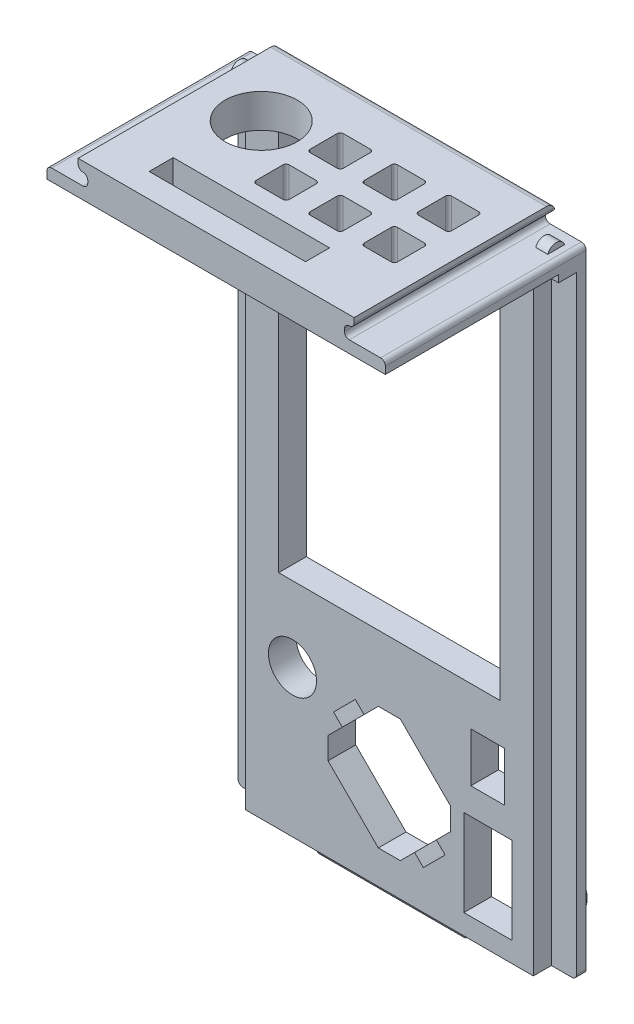
SolidWorks part; units mm, degrees
note: The reader was unsure of these and kept them because the rebuilt part matched: shared geometry of "草图2<3>".
ref_plane "前视基准面" through (0, 0, 0) normal (0, 0, 1) x (1, 0, 0)
ref_plane "上视基准面" through (0, 0, 0) normal (0, 1, 0) x (1, 0, 0)
ref_plane "右视基准面" through (0, 0, 0) normal (1, 0, 0) x (0, 0, -1)
sketch "草图1" plane through (0, 0, 0) normal (0, 0, 1) x (1, 0, 0)
  line L0 (0, -50.8) -> (0, 0)
  line L1 (0, -50.8) -> (27.94, -50.8)
  line L2 (27.94, -50.8) -> (27.94, 0)
  line L3 (0, 0) -> (27.94, 0)
  line L4 (14.67, -38.27) -> (13.27, -38.27)
  line L5 (13.27, -38.27) -> (13.97, -37.37)
  line L6 (13.97, -37.37) -> (14.67, -38.27)
  line L7 (18.77, -43.77) -> (18.77, -42.37)
  line L8 (18.77, -42.37) -> (19.67, -43.07)
  line L9 (19.67, -43.07) -> (18.77, -43.77)
  line L10 (9.17, -42.37) -> (9.17, -43.77)
  line L11 (9.17, -43.77) -> (8.27, -43.07)
  line L12 (8.27, -43.07) -> (9.17, -42.37)
  line L13 (13.27, -47.87) -> (14.67, -47.87)
  line L14 (14.67, -47.87) -> (13.97, -48.77)
  line L15 (13.97, -48.77) -> (13.27, -47.87)
  line L16 (4.5291, -38.6112) -> (4.5835, -38.6112)
  line L17 (4.5835, -38.6112) -> (4.5835, -38.6384)
  line L18 (4.5835, -38.6384) -> (4.6108, -38.6384)
  line L19 (4.6108, -38.6384) -> (4.6108, -38.6657)
  line L20 (4.6108, -38.6657) -> (4.638, -38.6657)
  line L21 (4.638, -38.6657) -> (4.638, -38.7201)
  line L22 (4.638, -38.7201) -> (4.6653, -38.7201)
  line L23 (4.6653, -38.7201) -> (4.6653, -38.9381)
  line L24 (4.6653, -38.9381) -> (4.6925, -38.9381)
  line L25 (4.6925, -38.9381) -> (4.6925, -39.1015)
  line L26 (4.6925, -39.1015) -> (4.7197, -39.1015)
  line L27 (4.7197, -39.1015) -> (4.7197, -39.1832)
  line L28 (4.7197, -39.1832) -> (4.747, -39.1832)
  line L29 (4.747, -39.1832) -> (4.747, -39.2921)
  line L30 (4.747, -39.2921) -> (4.7742, -39.2921)
  line L31 (4.7742, -39.2921) -> (4.7742, -39.3466)
  line L32 (4.7742, -39.3466) -> (4.8014, -39.3466)
  line L33 (4.8014, -39.3466) -> (4.8014, -39.3739)
  line L34 (4.8014, -39.3739) -> (4.8287, -39.3739)
  line L35 (4.8287, -39.3739) -> (4.8287, -39.4283)
  line L36 (4.8287, -39.4283) -> (4.8559, -39.4283)
  line L37 (4.8559, -39.4283) -> (4.8559, -39.4828)
  line L38 (4.8559, -39.4828) -> (4.8832, -39.4828)
  line L39 (4.8832, -39.4828) -> (4.8832, -39.51)
  line L40 (4.8832, -39.51) -> (4.9104, -39.51)
  line L41 (4.9104, -39.51) -> (4.9104, -39.5373)
  line L42 (4.9104, -39.5373) -> (4.9376, -39.5373)
  line L43 (4.9376, -39.5373) -> (4.9376, -39.5918)
  line L44 (4.9376, -39.5918) -> (4.9649, -39.5918)
  line L45 (4.9649, -39.5918) -> (4.9649, -39.619)
  line L46 (4.9649, -39.619) -> (4.9921, -39.619)
  line L47 (4.9921, -39.619) -> (4.9921, -39.6462)
  line L48 (4.9921, -39.6462) -> (5.0193, -39.6462)
  line L49 (5.0193, -39.6462) -> (5.0193, -39.6735)
  line L50 (5.0193, -39.6735) -> (5.0466, -39.6735)
  line L51 (5.0466, -39.6735) -> (5.0466, -39.7007)
  line L52 (5.0466, -39.7007) -> (5.0738, -39.7007)
  line L53 (5.0738, -39.7007) -> (5.0738, -39.7279)
  line L54 (5.0738, -39.7279) -> (5.1011, -39.7279)
  line L55 (5.1011, -39.7279) -> (5.1011, -39.7552)
  line L56 (5.1011, -39.7552) -> (5.1283, -39.7552)
  line L57 (5.1283, -39.7552) -> (5.1283, -39.7824)
  line L58 (5.1283, -39.7824) -> (5.1828, -39.7824)
  line L59 (5.1828, -39.7824) -> (5.1828, -39.8097)
  line L60 (5.1828, -39.8097) -> (5.21, -39.8097)
  line L61 (5.21, -39.8097) -> (5.21, -39.8369)
  line L62 (5.21, -39.8369) -> (5.2645, -39.8369)
  line L63 (5.2645, -39.8369) -> (5.2645, -39.8641)
  line L64 (5.2645, -39.8641) -> (5.319, -39.8641)
  line L65 (5.319, -39.8641) -> (5.319, -39.8914)
  line L66 (5.319, -39.8914) -> (5.3462, -39.8914)
  line L67 (5.3462, -39.8914) -> (5.3462, -39.9186)
  line L68 (5.3462, -39.9186) -> (5.4007, -39.9186)
  line L69 (5.4007, -39.9186) -> (5.4007, -39.9459)
  line L70 (5.4007, -39.9459) -> (5.4824, -39.9459)
  line L71 (5.4824, -39.9459) -> (5.4824, -39.9731)
  line L72 (5.4824, -39.9731) -> (5.5913, -39.9731)
  line L73 (5.5913, -39.9731) -> (5.5913, -40.0003)
  line L74 (5.5913, -40.0003) -> (5.7003, -40.0003)
  line L75 (5.7003, -40.0003) -> (5.7003, -40.0276)
  line L76 (5.7003, -40.0276) -> (6.1361, -40.0276)
  line L77 (6.1361, -40.0276) -> (6.1361, -40.0003)
  line L78 (6.1361, -40.0003) -> (6.2451, -40.0003)
  line L79 (6.2451, -40.0003) -> (6.2451, -39.9731)
  line L80 (6.2451, -39.9731) -> (6.354, -39.9731)
  line L81 (6.354, -39.9731) -> (6.354, -39.9459)
  line L82 (6.354, -39.9459) -> (6.4085, -39.9459)
  line L83 (6.4085, -39.9459) -> (6.4085, -39.9186)
  line L84 (6.4085, -39.9186) -> (6.463, -39.9186)
  line L85 (6.463, -39.9186) -> (6.463, -39.8914)
  line L86 (6.463, -39.8914) -> (6.5174, -39.8914)
  line L87 (6.5174, -39.8914) -> (6.5174, -39.8641)
  line L88 (6.5174, -39.8641) -> (6.5719, -39.8641)
  line L89 (6.5719, -39.8641) -> (6.5719, -39.8369)
  line L90 (6.5719, -39.8369) -> (6.6264, -39.8369)
  line L91 (6.6264, -39.8369) -> (6.6264, -39.8097)
  line L92 (6.6264, -39.8097) -> (6.6536, -39.8097)
  line L93 (6.6536, -39.8097) -> (6.6536, -39.7824)
  line L94 (6.6536, -39.7824) -> (6.6809, -39.7824)
  line L95 (6.6809, -39.7824) -> (6.6809, -39.7552)
  line L96 (6.6809, -39.7552) -> (6.7353, -39.7552)
  line L97 (6.7353, -39.7552) -> (6.7353, -39.7279)
  line L98 (6.7353, -39.7279) -> (6.7626, -39.7279)
  line L99 (6.7626, -39.7279) -> (6.7626, -39.7007)
  line L100 (6.7626, -39.7007) -> (6.7898, -39.7007)
  line L101 (6.7898, -39.7007) -> (6.7898, -39.6735)
  line L102 (6.7898, -39.6735) -> (6.8171, -39.6735)
  line L103 (6.8171, -39.6735) -> (6.8171, -39.6462)
  line L104 (6.8171, -39.6462) -> (6.8443, -39.6462)
  line L105 (6.8443, -39.6462) -> (6.8443, -39.619)
  line L106 (6.8443, -39.619) -> (6.8715, -39.619)
  line L107 (6.8715, -39.619) -> (6.8715, -39.5645)
  line L108 (6.8715, -39.5645) -> (6.8988, -39.5645)
  line L109 (6.8988, -39.5645) -> (6.8988, -39.5373)
  line L110 (6.8988, -39.5373) -> (6.926, -39.5373)
  line L111 (6.926, -39.5373) -> (6.926, -39.51)
  line L112 (6.926, -39.51) -> (6.9532, -39.51)
  line L113 (6.9532, -39.51) -> (6.9532, -39.4828)
  line L114 (6.9532, -39.4828) -> (6.9805, -39.4828)
  line L115 (6.9805, -39.4828) -> (6.9805, -39.4283)
  line L116 (6.9805, -39.4283) -> (7.0077, -39.4283)
  line L117 (7.0077, -39.4283) -> (7.0077, -39.3739)
  line L118 (7.0077, -39.3739) -> (7.035, -39.3739)
  line L119 (7.035, -39.3739) -> (7.035, -39.3194)
  line L120 (7.035, -39.3194) -> (7.0622, -39.3194)
  line L121 (7.0622, -39.3194) -> (7.0622, -39.2649)
  line L122 (7.0622, -39.2649) -> (7.0894, -39.2649)
  line L123 (7.0894, -39.2649) -> (7.0894, -39.1832)
  line L124 (7.0894, -39.1832) -> (7.1167, -39.1832)
  line L125 (7.1167, -39.1832) -> (7.1167, -39.1015)
  line L126 (7.1167, -39.1015) -> (7.1439, -39.1015)
  line L127 (7.1439, -39.1015) -> (7.1439, -38.9381)
  line L128 (7.1439, -38.9381) -> (7.1711, -38.9381)
  line L129 (7.1711, -38.9381) -> (7.1711, -38.7746)
  line L130 (7.1711, -38.7746) -> (7.1984, -38.7746)
  line L131 (7.1984, -38.7746) -> (7.1984, -38.7201)
  line L132 (7.1984, -38.7201) -> (7.2256, -38.7201)
  line L133 (7.2256, -38.7201) -> (7.2256, -38.6929)
  line L134 (7.2256, -38.6929) -> (7.2529, -38.6929)
  line L135 (7.2529, -38.6929) -> (7.2529, -38.6657)
  line L136 (7.2529, -38.6657) -> (7.4163, -38.6657)
  line L137 (7.4163, -38.6657) -> (7.4163, -38.6929)
  line L138 (7.4163, -38.6929) -> (7.4708, -38.6929)
  line L139 (7.4708, -38.6929) -> (7.4708, -38.7474)
  line L140 (7.4708, -38.7474) -> (7.498, -38.7474)
  line L141 (7.498, -38.7474) -> (7.498, -38.8019)
  line L142 (7.498, -38.8019) -> (7.5252, -38.8019)
  line L143 (7.5252, -38.8019) -> (7.5252, -38.8563)
  line L144 (7.5252, -38.8563) -> (7.498, -38.8563)
  line L145 (7.498, -38.8563) -> (7.498, -39.0742)
  line L146 (7.498, -39.0742) -> (7.4708, -39.0742)
  line L147 (7.4708, -39.0742) -> (7.4708, -39.1832)
  line L148 (7.4708, -39.1832) -> (7.4435, -39.1832)
  line L149 (7.4435, -39.1832) -> (7.4435, -39.2649)
  line L150 (7.4435, -39.2649) -> (7.4163, -39.2649)
  line L151 (7.4163, -39.2649) -> (7.4163, -39.3466)
  line L152 (7.4163, -39.3466) -> (7.389, -39.3466)
  line L153 (7.389, -39.3466) -> (7.389, -39.4283)
  line L154 (7.389, -39.4283) -> (7.3618, -39.4283)
  line L155 (7.3618, -39.4283) -> (7.3618, -39.4828)
  line L156 (7.3618, -39.4828) -> (7.3346, -39.4828)
  line L157 (7.3346, -39.4828) -> (7.3346, -39.5373)
  line L158 (7.3346, -39.5373) -> (7.3073, -39.5373)
  line L159 (7.3073, -39.5373) -> (7.3073, -39.5918)
  line L160 (7.3073, -39.5918) -> (7.2801, -39.5918)
  line L161 (7.2801, -39.5918) -> (7.2801, -39.6462)
  line L162 (7.2801, -39.6462) -> (7.2529, -39.6462)
  line L163 (7.2529, -39.6462) -> (7.2529, -39.6735)
  line L164 (7.2529, -39.6735) -> (7.2256, -39.6735)
  line L165 (7.2256, -39.6735) -> (7.2256, -39.7007)
  line L166 (7.2256, -39.7007) -> (7.1984, -39.7007)
  line L167 (7.1984, -39.7007) -> (7.1984, -39.7552)
  line L168 (7.1984, -39.7552) -> (7.1711, -39.7552)
  line L169 (7.1711, -39.7552) -> (7.1711, -39.7824)
  line L170 (7.1711, -39.7824) -> (7.1439, -39.7824)
  line L171 (7.1439, -39.7824) -> (7.1439, -39.8097)
  line L172 (7.1439, -39.8097) -> (7.1167, -39.8097)
  line L173 (7.1167, -39.8097) -> (7.1167, -39.8641)
  line L174 (7.1167, -39.8641) -> (7.0894, -39.8641)
  line L175 (7.0894, -39.8641) -> (7.0894, -39.8914)
  line L176 (7.0894, -39.8914) -> (7.035, -39.8914)
  line L177 (7.035, -39.8914) -> (7.035, -39.9186)
  line L178 (7.035, -39.9186) -> (7.0077, -39.9186)
  line L179 (7.0077, -39.9186) -> (7.0077, -39.9459)
  line L180 (7.0077, -39.9459) -> (6.9805, -39.9459)
  line L181 (6.9805, -39.9459) -> (6.9805, -39.9731)
  line L182 (6.9805, -39.9731) -> (6.9532, -39.9731)
  line L183 (6.9532, -39.9731) -> (6.9532, -40.0003)
  line L184 (6.9532, -40.0003) -> (6.926, -40.0003)
  line L185 (6.926, -40.0003) -> (6.926, -40.0276)
  line L186 (6.926, -40.0276) -> (6.8988, -40.0276)
  line L187 (6.8988, -40.0276) -> (6.8988, -40.0548)
  line L188 (6.8988, -40.0548) -> (6.8443, -40.0548)
  line L189 (6.8443, -40.0548) -> (6.8443, -40.082)
  line L190 (6.8443, -40.082) -> (6.8171, -40.082)
  line L191 (6.8171, -40.082) -> (6.8171, -40.1093)
  line L192 (6.8171, -40.1093) -> (6.7626, -40.1093)
  line L193 (6.7626, -40.1093) -> (6.7626, -40.1365)
  line L194 (6.7626, -40.1365) -> (6.7353, -40.1365)
  line L195 (6.7353, -40.1365) -> (6.7353, -40.1638)
  line L196 (6.7353, -40.1638) -> (6.6809, -40.1638)
  line L197 (6.6809, -40.1638) -> (6.6809, -40.191)
  line L198 (6.6809, -40.191) -> (6.6264, -40.191)
  line L199 (6.6264, -40.191) -> (6.6264, -40.2182)
  line L200 (6.6264, -40.2182) -> (6.5719, -40.2182)
  line L201 (6.5719, -40.2182) -> (6.5719, -40.2455)
  line L202 (6.5719, -40.2455) -> (6.5174, -40.2455)
  line L203 (6.5174, -40.2455) -> (6.5174, -40.2727)
  line L204 (6.5174, -40.2727) -> (6.4357, -40.2727)
  line L205 (6.4357, -40.2727) -> (6.4357, -40.2999)
  line L206 (6.4357, -40.2999) -> (6.354, -40.2999)
  line L207 (6.354, -40.2999) -> (6.354, -40.3272)
  line L208 (6.354, -40.3272) -> (6.2178, -40.3272)
  line L209 (6.2178, -40.3272) -> (6.2178, -40.3544)
  line L210 (6.2178, -40.3544) -> (6.1089, -40.3544)
  line L211 (6.1089, -40.3544) -> (6.1089, -40.7902)
  line L212 (6.1089, -40.7902) -> (6.4357, -40.7902)
  line L213 (6.4357, -40.7902) -> (6.4357, -40.8175)
  line L214 (6.4357, -40.8175) -> (6.5174, -40.8175)
  line L215 (6.5174, -40.8175) -> (6.5174, -40.8447)
  line L216 (6.5174, -40.8447) -> (6.5447, -40.8447)
  line L217 (6.5447, -40.8447) -> (6.5447, -40.8719)
  line L218 (6.5447, -40.8719) -> (6.5719, -40.8719)
  line L219 (6.5719, -40.8719) -> (6.5719, -40.8992)
  line L220 (6.5719, -40.8992) -> (6.5991, -40.8992)
  line L221 (6.5991, -40.8992) -> (6.5991, -41.0898)
  line L222 (6.5991, -41.0898) -> (6.5719, -41.0898)
  line L223 (6.5719, -41.0898) -> (6.5719, -41.1443)
  line L224 (6.5719, -41.1443) -> (6.5447, -41.1443)
  line L225 (6.5447, -41.1443) -> (6.5447, -41.1716)
  line L226 (6.5447, -41.1716) -> (6.4902, -41.1716)
  line L227 (6.4902, -41.1716) -> (6.4902, -41.1988)
  line L228 (6.4902, -41.1988) -> (5.3462, -41.1988)
  line L229 (5.3462, -41.1988) -> (5.3462, -41.1716)
  line L230 (5.3462, -41.1716) -> (5.2917, -41.1716)
  line L231 (5.2917, -41.1716) -> (5.2917, -41.1443)
  line L232 (5.2917, -41.1443) -> (5.2645, -41.1443)
  line L233 (5.2645, -41.1443) -> (5.2645, -41.0898)
  line L234 (5.2645, -41.0898) -> (5.2372, -41.0898)
  line L235 (5.2372, -41.0898) -> (5.2372, -40.8992)
  line L236 (5.2372, -40.8992) -> (5.2645, -40.8992)
  line L237 (5.2645, -40.8992) -> (5.2645, -40.8719)
  line L238 (5.2645, -40.8719) -> (5.2917, -40.8719)
  line L239 (5.2917, -40.8719) -> (5.2917, -40.8447)
  line L240 (5.2917, -40.8447) -> (5.319, -40.8447)
  line L241 (5.319, -40.8447) -> (5.319, -40.8175)
  line L242 (5.319, -40.8175) -> (5.4007, -40.8175)
  line L243 (5.4007, -40.8175) -> (5.4007, -40.7902)
  line L244 (5.4007, -40.7902) -> (5.7003, -40.7902)
  line L245 (5.7003, -40.7902) -> (5.7003, -40.3544)
  line L246 (5.7003, -40.3544) -> (5.5913, -40.3544)
  line L247 (5.5913, -40.3544) -> (5.5913, -40.3272)
  line L248 (5.5913, -40.3272) -> (5.4824, -40.3272)
  line L249 (5.4824, -40.3272) -> (5.4824, -40.2999)
  line L250 (5.4824, -40.2999) -> (5.4007, -40.2999)
  line L251 (5.4007, -40.2999) -> (5.4007, -40.2727)
  line L252 (5.4007, -40.2727) -> (5.319, -40.2727)
  line L253 (5.319, -40.2727) -> (5.319, -40.2455)
  line L254 (5.319, -40.2455) -> (5.2645, -40.2455)
  line L255 (5.2645, -40.2455) -> (5.2645, -40.2182)
  line L256 (5.2645, -40.2182) -> (5.21, -40.2182)
  line L257 (5.21, -40.2182) -> (5.21, -40.191)
  line L258 (5.21, -40.191) -> (5.1555, -40.191)
  line L259 (5.1555, -40.191) -> (5.1555, -40.1638)
  line L260 (5.1555, -40.1638) -> (5.1011, -40.1638)
  line L261 (5.1011, -40.1638) -> (5.1011, -40.1365)
  line L262 (5.1011, -40.1365) -> (5.0466, -40.1365)
  line L263 (5.0466, -40.1365) -> (5.0466, -40.1093)
  line L264 (5.0466, -40.1093) -> (5.0193, -40.1093)
  line L265 (5.0193, -40.1093) -> (5.0193, -40.082)
  line L266 (5.0193, -40.082) -> (4.9649, -40.082)
  line L267 (4.9649, -40.082) -> (4.9649, -40.0548)
  line L268 (4.9649, -40.0548) -> (4.9376, -40.0548)
  line L269 (4.9376, -40.0548) -> (4.9376, -40.0276)
  line L270 (4.9376, -40.0276) -> (4.9104, -40.0276)
  line L271 (4.9104, -40.0276) -> (4.9104, -40.0003)
  line L272 (4.9104, -40.0003) -> (4.8832, -40.0003)
  line L273 (4.8832, -40.0003) -> (4.8832, -39.9731)
  line L274 (4.8832, -39.9731) -> (4.8287, -39.9731)
  line L275 (4.8287, -39.9731) -> (4.8287, -39.9459)
  line L276 (4.8287, -39.9459) -> (4.8014, -39.9459)
  line L277 (4.8014, -39.9459) -> (4.8014, -39.9186)
  line L278 (4.8014, -39.9186) -> (4.7742, -39.9186)
  line L279 (4.7742, -39.9186) -> (4.7742, -39.8914)
  line L280 (4.7742, -39.8914) -> (4.747, -39.8914)
  line L281 (4.747, -39.8914) -> (4.747, -39.8641)
  line L282 (4.747, -39.8641) -> (4.7197, -39.8641)
  line L283 (4.7197, -39.8641) -> (4.7197, -39.8097)
  line L284 (4.7197, -39.8097) -> (4.6925, -39.8097)
  line L285 (4.6925, -39.8097) -> (4.6925, -39.7824)
  line L286 (4.6925, -39.7824) -> (4.6653, -39.7824)
  line L287 (4.6653, -39.7824) -> (4.6653, -39.7552)
  line L288 (4.6653, -39.7552) -> (4.638, -39.7552)
  line L289 (4.638, -39.7552) -> (4.638, -39.7279)
  line L290 (4.638, -39.7279) -> (4.6108, -39.7279)
  line L291 (4.6108, -39.7279) -> (4.6108, -39.6735)
  line L292 (4.6108, -39.6735) -> (4.5835, -39.6735)
  line L293 (4.5835, -39.6735) -> (4.5835, -39.6462)
  line L294 (4.5835, -39.6462) -> (4.5563, -39.6462)
  line L295 (4.5563, -39.6462) -> (4.5563, -39.5918)
  line L296 (4.5563, -39.5918) -> (4.5291, -39.5918)
  line L297 (4.5291, -39.5918) -> (4.5291, -39.5645)
  line L298 (4.5291, -39.5645) -> (4.5018, -39.5645)
  line L299 (4.5018, -39.5645) -> (4.5018, -39.51)
  line L300 (4.5018, -39.51) -> (4.4746, -39.51)
  line L301 (4.4746, -39.51) -> (4.4746, -39.4283)
  line L302 (4.4746, -39.4283) -> (4.4473, -39.4283)
  line L303 (4.4473, -39.4283) -> (4.4473, -39.3739)
  line L304 (4.4473, -39.3739) -> (4.4201, -39.3739)
  line L305 (4.4201, -39.3739) -> (4.4201, -39.2921)
  line L306 (4.4201, -39.2921) -> (4.3929, -39.2921)
  line L307 (4.3929, -39.2921) -> (4.3929, -39.2104)
  line L308 (4.3929, -39.2104) -> (4.3656, -39.2104)
  line L309 (4.3656, -39.2104) -> (4.3656, -39.1015)
  line L310 (4.3656, -39.1015) -> (4.3384, -39.1015)
  line L311 (4.3384, -39.1015) -> (4.3384, -38.8836)
  line L312 (4.3384, -38.8836) -> (4.3112, -38.8836)
  line L313 (4.3112, -38.8836) -> (4.3112, -38.7474)
  line L314 (4.3112, -38.7474) -> (4.3384, -38.7474)
  line L315 (4.3384, -38.7474) -> (4.3384, -38.6657)
  line L316 (4.3384, -38.6657) -> (4.3656, -38.6657)
  line L317 (4.3656, -38.6657) -> (4.3656, -38.6384)
  line L318 (4.3656, -38.6384) -> (4.3929, -38.6384)
  line L319 (4.3929, -38.6384) -> (4.3929, -38.6112)
  line L320 (4.3929, -38.6112) -> (4.4473, -38.6112)
  line L321 (4.4473, -38.6112) -> (4.4473, -38.584)
  line L322 (4.4473, -38.584) -> (4.5291, -38.584)
  line L323 (4.5291, -38.584) -> (4.5291, -38.6112)
  line L324 (6.0544, -36.5411) -> (6.1633, -36.5411)
  line L325 (6.1633, -36.5411) -> (6.1633, -36.5683)
  line L326 (6.1633, -36.5683) -> (6.2451, -36.5683)
  line L327 (6.2451, -36.5683) -> (6.2451, -36.5956)
  line L328 (6.2451, -36.5956) -> (6.2995, -36.5956)
  line L329 (6.2995, -36.5956) -> (6.2995, -36.6228)
  line L330 (6.2995, -36.6228) -> (6.354, -36.6228)
  line L331 (6.354, -36.6228) -> (6.354, -36.6501)
  line L332 (6.354, -36.6501) -> (6.3812, -36.6501)
  line L333 (6.3812, -36.6501) -> (6.3812, -36.6773)
  line L334 (6.3812, -36.6773) -> (6.4357, -36.6773)
  line L335 (6.4357, -36.6773) -> (6.4357, -36.7045)
  line L336 (6.4357, -36.7045) -> (6.463, -36.7045)
  line L337 (6.463, -36.7045) -> (6.463, -36.7318)
  line L338 (6.463, -36.7318) -> (6.4902, -36.7318)
  line L339 (6.4902, -36.7318) -> (6.4902, -36.759)
  line L340 (6.4902, -36.759) -> (6.5174, -36.759)
  line L341 (6.5174, -36.759) -> (6.5174, -36.7863)
  line L342 (6.5174, -36.7863) -> (6.5447, -36.7863)
  line L343 (6.5447, -36.7863) -> (6.5447, -36.8135)
  line L344 (6.5447, -36.8135) -> (6.5719, -36.8135)
  line L345 (6.5719, -36.8135) -> (6.5719, -36.868)
  line L346 (6.5719, -36.868) -> (6.5991, -36.868)
  line L347 (6.5991, -36.868) -> (6.5991, -36.8952)
  line L348 (6.5991, -36.8952) -> (6.6264, -36.8952)
  line L349 (6.6264, -36.8952) -> (6.6264, -36.9497)
  line L350 (6.6264, -36.9497) -> (6.6536, -36.9497)
  line L351 (6.6536, -36.9497) -> (6.6536, -36.9769)
  line L352 (6.6536, -36.9769) -> (6.6809, -36.9769)
  line L353 (6.6809, -36.9769) -> (6.6809, -37.0314)
  line L354 (6.6809, -37.0314) -> (6.7081, -37.0314)
  line L355 (6.7081, -37.0314) -> (6.7081, -37.1403)
  line L356 (6.7081, -37.1403) -> (6.7353, -37.1403)
  line L357 (6.7353, -37.1403) -> (6.7353, -38.9925)
  line L358 (6.7353, -38.9925) -> (6.7081, -38.9925)
  line L359 (6.7081, -38.9925) -> (6.7081, -39.0742)
  line L360 (6.7081, -39.0742) -> (6.6809, -39.0742)
  line L361 (6.6809, -39.0742) -> (6.6809, -39.156)
  line L362 (6.6809, -39.156) -> (6.6536, -39.156)
  line L363 (6.6536, -39.156) -> (6.6536, -39.1832)
  line L364 (6.6536, -39.1832) -> (6.6264, -39.1832)
  line L365 (6.6264, -39.1832) -> (6.6264, -39.2377)
  line L366 (6.6264, -39.2377) -> (6.5991, -39.2377)
  line L367 (6.5991, -39.2377) -> (6.5991, -39.2921)
  line L368 (6.5991, -39.2921) -> (6.5719, -39.2921)
  line L369 (6.5719, -39.2921) -> (6.5719, -39.3194)
  line L370 (6.5719, -39.3194) -> (6.5447, -39.3194)
  line L371 (6.5447, -39.3194) -> (6.5447, -39.3466)
  line L372 (6.5447, -39.3466) -> (6.5174, -39.3466)
  line L373 (6.5174, -39.3466) -> (6.5174, -39.3739)
  line L374 (6.5174, -39.3739) -> (6.4902, -39.3739)
  line L375 (6.4902, -39.3739) -> (6.4902, -39.4011)
  line L376 (6.4902, -39.4011) -> (6.463, -39.4011)
  line L377 (6.463, -39.4011) -> (6.463, -39.4283)
  line L378 (6.463, -39.4283) -> (6.4357, -39.4283)
  line L379 (6.4357, -39.4283) -> (6.4357, -39.4556)
  line L380 (6.4357, -39.4556) -> (6.3812, -39.4556)
  line L381 (6.3812, -39.4556) -> (6.3812, -39.4828)
  line L382 (6.3812, -39.4828) -> (6.354, -39.4828)
  line L383 (6.354, -39.4828) -> (6.354, -39.51)
  line L384 (6.354, -39.51) -> (6.2995, -39.51)
  line L385 (6.2995, -39.51) -> (6.2995, -39.5373)
  line L386 (6.2995, -39.5373) -> (6.2451, -39.5373)
  line L387 (6.2451, -39.5373) -> (6.2451, -39.5645)
  line L388 (6.2451, -39.5645) -> (6.1633, -39.5645)
  line L389 (6.1633, -39.5645) -> (6.1633, -39.5918)
  line L390 (6.1633, -39.5918) -> (6.0544, -39.5918)
  line L391 (6.0544, -39.5918) -> (6.0544, -39.619)
  line L392 (6.0544, -39.619) -> (5.782, -39.619)
  line L393 (5.782, -39.619) -> (5.782, -39.5918)
  line L394 (5.782, -39.5918) -> (5.6731, -39.5918)
  line L395 (5.6731, -39.5918) -> (5.6731, -39.5645)
  line L396 (5.6731, -39.5645) -> (5.5913, -39.5645)
  line L397 (5.5913, -39.5645) -> (5.5913, -39.5373)
  line L398 (5.5913, -39.5373) -> (5.5369, -39.5373)
  line L399 (5.5369, -39.5373) -> (5.5369, -39.51)
  line L400 (5.5369, -39.51) -> (5.4824, -39.51)
  line L401 (5.4824, -39.51) -> (5.4824, -39.4828)
  line L402 (5.4824, -39.4828) -> (5.4279, -39.4828)
  line L403 (5.4279, -39.4828) -> (5.4279, -39.4556)
  line L404 (5.4279, -39.4556) -> (5.4007, -39.4556)
  line L405 (5.4007, -39.4556) -> (5.4007, -39.4283)
  line L406 (5.4007, -39.4283) -> (5.3734, -39.4283)
  line L407 (5.3734, -39.4283) -> (5.3734, -39.4011)
  line L408 (5.3734, -39.4011) -> (5.3462, -39.4011)
  line L409 (5.3462, -39.4011) -> (5.3462, -39.3739)
  line L410 (5.3462, -39.3739) -> (5.319, -39.3739)
  line L411 (5.319, -39.3739) -> (5.319, -39.3466)
  line L412 (5.319, -39.3466) -> (5.2917, -39.3466)
  line L413 (5.2917, -39.3466) -> (5.2917, -39.3194)
  line L414 (5.2917, -39.3194) -> (5.2645, -39.3194)
  line L415 (5.2645, -39.3194) -> (5.2645, -39.2921)
  line L416 (5.2645, -39.2921) -> (5.2372, -39.2921)
  line L417 (5.2372, -39.2921) -> (5.2372, -39.2377)
  line L418 (5.2372, -39.2377) -> (5.21, -39.2377)
  line L419 (5.21, -39.2377) -> (5.21, -39.2104)
  line L420 (5.21, -39.2104) -> (5.1828, -39.2104)
  line L421 (5.1828, -39.2104) -> (5.1828, -39.156)
  line L422 (5.1828, -39.156) -> (5.1555, -39.156)
  line L423 (5.1555, -39.156) -> (5.1555, -39.0742)
  line L424 (5.1555, -39.0742) -> (5.1283, -39.0742)
  line L425 (5.1283, -39.0742) -> (5.1283, -38.9925)
  line L426 (5.1283, -38.9925) -> (5.1011, -38.9925)
  line L427 (5.1011, -38.9925) -> (5.1011, -38.8291)
  line L428 (5.1011, -38.8291) -> (5.0738, -38.8291)
  line L429 (5.0738, -38.8291) -> (5.0738, -37.3038)
  line L430 (5.0738, -37.3038) -> (5.1011, -37.3038)
  line L431 (5.1011, -37.3038) -> (5.1011, -37.1403)
  line L432 (5.1011, -37.1403) -> (5.1283, -37.1403)
  line L433 (5.1283, -37.1403) -> (5.1283, -37.0314)
  line L434 (5.1283, -37.0314) -> (5.1555, -37.0314)
  line L435 (5.1555, -37.0314) -> (5.1555, -36.9769)
  line L436 (5.1555, -36.9769) -> (5.1828, -36.9769)
  line L437 (5.1828, -36.9769) -> (5.1828, -36.9224)
  line L438 (5.1828, -36.9224) -> (5.21, -36.9224)
  line L439 (5.21, -36.9224) -> (5.21, -36.868)
  line L440 (5.21, -36.868) -> (5.2372, -36.868)
  line L441 (5.2372, -36.868) -> (5.2372, -36.8407)
  line L442 (5.2372, -36.8407) -> (5.2645, -36.8407)
  line L443 (5.2645, -36.8407) -> (5.2645, -36.8135)
  line L444 (5.2645, -36.8135) -> (5.2917, -36.8135)
  line L445 (5.2917, -36.8135) -> (5.2917, -36.7863)
  line L446 (5.2917, -36.7863) -> (5.319, -36.7863)
  line L447 (5.319, -36.7863) -> (5.319, -36.759)
  line L448 (5.319, -36.759) -> (5.3462, -36.759)
  line L449 (5.3462, -36.759) -> (5.3462, -36.7318)
  line L450 (5.3462, -36.7318) -> (5.3734, -36.7318)
  line L451 (5.3734, -36.7318) -> (5.3734, -36.7045)
  line L452 (5.3734, -36.7045) -> (5.4007, -36.7045)
  line L453 (5.4007, -36.7045) -> (5.4007, -36.6773)
  line L454 (5.4007, -36.6773) -> (5.4279, -36.6773)
  line L455 (5.4279, -36.6773) -> (5.4279, -36.6501)
  line L456 (5.4279, -36.6501) -> (5.4824, -36.6501)
  line L457 (5.4824, -36.6501) -> (5.4824, -36.6228)
  line L458 (5.4824, -36.6228) -> (5.5369, -36.6228)
  line L459 (5.5369, -36.6228) -> (5.5369, -36.5956)
  line L460 (5.5369, -36.5956) -> (5.5913, -36.5956)
  line L461 (5.5913, -36.5956) -> (5.5913, -36.5683)
  line L462 (5.5913, -36.5683) -> (5.6731, -36.5683)
  line L463 (5.6731, -36.5683) -> (5.6731, -36.5411)
  line L464 (5.6731, -36.5411) -> (5.782, -36.5411)
  line L465 (5.782, -36.5411) -> (5.782, -36.5139)
  line L466 (5.782, -36.5139) -> (6.0544, -36.5139)
  line L467 (6.0544, -36.5139) -> (6.0544, -36.5411)
  line L468 (9.4168, 0.0508) -> (9.4168, 2.0508)
  line L469 (5.4168, 2.0508) -> (9.4168, 2.0508)
  line L470 (5.4168, 0.0508) -> (5.4168, 2.0508)
  line L471 (10.4168, -11.9492) -> (10.4168, 0.0508)
  line L472 (4.4148, 0.0508) -> (10.4168, 0.0508)
  line L473 (4.4148, -11.9492) -> (4.4148, 0.0508)
  line L474 (4.4148, -11.9492) -> (10.4168, -11.9492)
  line L475 (20.67, -47.67) -> (20.67, -43.67)
  line L476 (23.67, -47.67) -> (23.67, -43.67)
  line L477 (23.2716, -46.9684) -> (23.2716, -48.7716)
  line L478 (23.2716, -48.7716) -> (21.0684, -48.7716)
  line L479 (21.0684, -48.7716) -> (21.0684, -46.9684)
  line L480 (21.0684, -46.9684) -> (23.2716, -46.9684)
  line L481 (23.2716, -42.5684) -> (23.2716, -44.3716)
  line L482 (23.2716, -44.3716) -> (21.0684, -44.3716)
  line L483 (21.0684, -44.3716) -> (21.0684, -42.5684)
  line L484 (21.0684, -42.5684) -> (23.2716, -42.5684)
  line L485 (16.2151, -45.3235) -> (16.2151, -44.4254)
  line L486 (15.317, -45.3235) -> (16.2151, -44.4254)
  line L487 (15.317, -45.3235) -> (16.2151, -45.3235)
  line L488 (13.97, -43.0784) -> (13.97, -41.6642)
  line L489 (13.97, -41.6642) -> (14.3236, -42.0177)
  line L490 (13.6164, -42.0177) -> (14.3236, -42.0177)
  line L491 (13.6164, -42.0177) -> (13.97, -41.6642)
  line L492 (12.5558, -43.0784) -> (13.97, -43.0784)
  line L493 (12.5558, -43.0784) -> (12.9093, -42.7248)
  line L494 (12.9093, -43.432) -> (12.9093, -42.7248)
  line L495 (12.5558, -43.0784) -> (12.9093, -43.432)
  line L496 (13.97, -44.4926) -> (13.97, -43.0784)
  line L497 (13.6164, -44.1391) -> (13.97, -44.4926)
  line L498 (13.6164, -44.1391) -> (14.3236, -44.1391)
  line L499 (13.97, -44.4926) -> (14.3236, -44.1391)
  line L500 (15.0307, -42.7248) -> (15.3842, -43.0784)
  line L501 (15.0307, -43.432) -> (15.0307, -42.7248)
  line L502 (15.0307, -43.432) -> (15.3842, -43.0784)
  line L503 (13.97, -43.0784) -> (15.3842, -43.0784)
  line L504 (14.6771, -38.4822) -> (18.5662, -42.3713)
  line L505 (13.2629, -38.4822) -> (14.6771, -38.4822)
  line L506 (9.3738, -42.3713) -> (13.2629, -38.4822)
  line L507 (9.3738, -43.7855) -> (13.2629, -47.6746)
  line L508 (9.3738, -43.7855) -> (9.3738, -42.3713)
  line L509 (18.5662, -43.7855) -> (18.5662, -42.3713)
  line L510 (14.6771, -47.6746) -> (18.5662, -43.7855)
  line L511 (13.2629, -47.6746) -> (14.6771, -47.6746)
  line L512 (10.0385, -40.25) -> (11.1416, -39.1469)
  line L513 (11.1416, -39.1469) -> (12.2447, -40.25)
  line L514 (12.2447, -40.25) -> (11.1416, -41.3531)
  line L515 (11.1416, -41.3531) -> (10.0385, -40.25)
  line L516 (15.6953, -45.9068) -> (16.7984, -44.8037)
  line L517 (16.7984, -44.8037) -> (17.9015, -45.9068)
  line L518 (17.9015, -45.9068) -> (16.7984, -47.0099)
  line L519 (16.7984, -47.0099) -> (15.6953, -45.9068)
  line L520 (16.155, -42.1238) -> (17.6116, -40.6672)
  line L521 (17.6116, -40.6672) -> (18.3611, -41.4167)
  line L522 (18.3611, -41.4167) -> (16.9045, -42.8733)
  line L523 (16.9045, -42.8733) -> (16.155, -42.1238)
  line L524 (15.165, -41.1339) -> (16.6217, -39.6772)
  line L525 (16.6217, -39.6772) -> (17.3712, -40.4267)
  line L526 (17.3712, -40.4267) -> (15.9145, -41.8834)
  line L527 (15.9145, -41.8834) -> (15.165, -41.1339)
  line L528 (14.1751, -40.1439) -> (15.6317, -38.6873)
  line L529 (15.6317, -38.6873) -> (16.3812, -39.4368)
  line L530 (16.3812, -39.4368) -> (14.9246, -40.8934)
  line L531 (14.9246, -40.8934) -> (14.1751, -40.1439)
  line L532 (9.5789, -44.7401) -> (11.0355, -43.2835)
  line L533 (11.0355, -43.2835) -> (11.785, -44.033)
  line L534 (11.785, -44.033) -> (10.3284, -45.4896)
  line L535 (10.3284, -45.4896) -> (9.5789, -44.7401)
  line L536 (10.5688, -45.7301) -> (12.0255, -44.2734)
  line L537 (12.0255, -44.2734) -> (12.775, -45.0229)
  line L538 (12.775, -45.0229) -> (11.3183, -46.4796)
  line L539 (11.3183, -46.4796) -> (10.5688, -45.7301)
  line L540 (11.5588, -46.72) -> (13.0154, -45.2634)
  line L541 (13.0154, -45.2634) -> (13.7649, -46.0129)
  line L542 (13.7649, -46.0129) -> (12.3083, -47.4695)
  line L543 (12.3083, -47.4695) -> (11.5588, -46.72)
  line L544 (22.895, -37.988) -> (22.895, -37.628)
  line L545 (21.395, -37.988) -> (21.395, -37.628)
  line L546 (21.645, -37.6072) -> (22.645, -37.6072)
  line L547 (21.764, -37.9858) -> (22.145, -37.6048)
  line L548 (22.145, -37.6048) -> (22.526, -37.9858)
  line L549 (21.764, -37.9858) -> (22.526, -37.9858)
  line L550 (22.1466, -38.1564) -> (22.1466, -39.3596)
  line L551 (22.1466, -39.3596) -> (21.2434, -39.3596)
  line L552 (21.2434, -39.3596) -> (21.2434, -38.1564)
  line L553 (21.2434, -38.1564) -> (22.1466, -38.1564)
  line L554 (22.1466, -36.2564) -> (22.1466, -37.4596)
  line L555 (22.1466, -37.4596) -> (21.2434, -37.4596)
  line L556 (21.2434, -37.4596) -> (21.2434, -36.2564)
  line L557 (21.2434, -36.2564) -> (22.1466, -36.2564)
  line L558 (23.0466, -36.2564) -> (23.0466, -37.4596)
  line L559 (23.0466, -37.4596) -> (22.1434, -37.4596)
  line L560 (22.1434, -37.4596) -> (22.1434, -36.2564)
  line L561 (22.1434, -36.2564) -> (23.0466, -36.2564)
  line L562 (23.0466, -38.1564) -> (23.0466, -39.3596)
  line L563 (23.0466, -39.3596) -> (22.1434, -39.3596)
  line L564 (22.1434, -39.3596) -> (22.1434, -38.1564)
  line L565 (22.1434, -38.1564) -> (23.0466, -38.1564)
  circle A0 centre (0, -50.8) radius 0.0375
  circle A1 centre (0, 0) radius 0.0375
  circle A2 centre (0, -50.8) radius 0.0375
  circle A3 centre (27.94, -50.8) radius 0.0375
  circle A4 centre (27.94, -50.8) radius 0.0375
  circle A5 centre (27.94, 0) radius 0.0375
  circle A6 centre (0, 0) radius 0.0375
  circle A7 centre (27.94, 0) radius 0.0375
  circle A8 centre (5.9182, -38.735) radius 0.6365
  circle A9 centre (6.5547, -38.735) radius 0.0635
  circle A10 centre (5.2817, -38.735) radius 0.0635
  circle A11 centre (20.6248, -38.0746) radius 0.3302
  circle A12 centre (9.4168, 0.0508) radius 0.0635
  circle A13 centre (9.4168, 2.0508) radius 0.0635
  circle A14 centre (5.4168, 2.0508) radius 0.0635
  circle A15 centre (9.4168, 2.0508) radius 0.0635
  circle A16 centre (5.4168, 0.0508) radius 0.0635
  circle A17 centre (5.4168, 2.0508) radius 0.0635
  circle A18 centre (10.4168, -11.9492) radius 0.0635
  circle A19 centre (10.4168, 0.0508) radius 0.0635
  circle A20 centre (4.4148, 0.0508) radius 0.0635
  circle A21 centre (10.4168, 0.0508) radius 0.0635
  circle A22 centre (4.4148, -11.9492) radius 0.0635
  circle A23 centre (4.4148, 0.0508) radius 0.0635
  circle A24 centre (4.4148, -11.9492) radius 0.0635
  circle A25 centre (10.4168, -11.9492) radius 0.0635
  circle A26 centre (7.4168, -8.9492) radius 0.5
  circle A27 centre (7.4168, -9.4492) radius 0.0318
  circle A28 centre (7.4168, -8.4492) radius 0.0317
  circle A29 centre (7.4168, -2.9492) radius 0.5
  circle A30 centre (7.4168, -3.4492) radius 0.0318
  circle A31 centre (7.4168, -2.4492) radius 0.0318
  circle A32 centre (20.67, -47.67) radius 0.0635
  circle A33 centre (20.67, -43.67) radius 0.0635
  circle A34 centre (23.67, -47.67) radius 0.0635
  circle A35 centre (23.67, -43.67) radius 0.0635
  circle A36 centre (22.17, -45.67) radius 0.7071
  circle A37 centre (22.17, -46.3771) radius 0.0635
  circle A38 centre (22.17, -44.9629) radius 0.0635
  circle A39 centre (16.2151, -45.3235) radius 0.0635
  circle A40 centre (16.2151, -44.4254) radius 0.0635
  circle A41 centre (15.317, -45.3235) radius 0.0635
  circle A42 centre (16.2151, -44.4254) radius 0.0635
  circle A43 centre (15.317, -45.3235) radius 0.0635
  circle A44 centre (16.2151, -45.3235) radius 0.0635
  circle A45 centre (13.97, -43.0784) radius 0.0635
  circle A46 centre (13.97, -41.6642) radius 0.0635
  circle A47 centre (13.97, -41.6642) radius 0.0635
  circle A48 centre (14.3236, -42.0177) radius 0.0635
  circle A49 centre (13.6164, -42.0177) radius 0.0635
  circle A50 centre (14.3236, -42.0177) radius 0.0635
  circle A51 centre (13.6164, -42.0177) radius 0.0635
  circle A52 centre (13.97, -41.6642) radius 0.0635
  circle A53 centre (12.5558, -43.0784) radius 0.0635
  circle A54 centre (13.97, -43.0784) radius 0.0635
  circle A55 centre (12.5558, -43.0784) radius 0.0635
  circle A56 centre (12.9093, -42.7248) radius 0.0635
  circle A57 centre (12.9093, -43.432) radius 0.0635
  circle A58 centre (12.9093, -42.7248) radius 0.0635
  circle A59 centre (12.5558, -43.0784) radius 0.0635
  circle A60 centre (12.9093, -43.432) radius 0.0635
  circle A61 centre (13.97, -44.4926) radius 0.0635
  circle A62 centre (13.97, -43.0784) radius 0.0635
  circle A63 centre (13.6164, -44.1391) radius 0.0635
  circle A64 centre (13.97, -44.4926) radius 0.0635
  circle A65 centre (13.6164, -44.1391) radius 0.0635
  circle A66 centre (14.3236, -44.1391) radius 0.0635
  circle A67 centre (13.97, -44.4926) radius 0.0635
  circle A68 centre (14.3236, -44.1391) radius 0.0635
  circle A69 centre (15.0307, -42.7248) radius 0.0635
  circle A70 centre (15.3842, -43.0784) radius 0.0635
  circle A71 centre (15.0307, -43.432) radius 0.0635
  circle A72 centre (15.0307, -42.7248) radius 0.0635
  circle A73 centre (15.0307, -43.432) radius 0.0635
  circle A74 centre (15.3842, -43.0784) radius 0.0635
  circle A75 centre (13.97, -43.0784) radius 0.0635
  circle A76 centre (15.3842, -43.0784) radius 0.0635
  circle A77 centre (14.6771, -38.4822) radius 0.0635
  circle A78 centre (18.5662, -42.3713) radius 0.0635
  circle A79 centre (13.2629, -38.4822) radius 0.0635
  circle A80 centre (14.6771, -38.4822) radius 0.0635
  circle A81 centre (9.3738, -42.3713) radius 0.0635
  circle A82 centre (13.2629, -38.4822) radius 0.0635
  circle A83 centre (9.3738, -43.7855) radius 0.0635
  circle A84 centre (13.2629, -47.6746) radius 0.0635
  circle A85 centre (9.3738, -43.7855) radius 0.0635
  circle A86 centre (9.3738, -42.3713) radius 0.0635
  circle A87 centre (18.5662, -43.7855) radius 0.0635
  circle A88 centre (18.5662, -42.3713) radius 0.0635
  circle A89 centre (14.6771, -47.6746) radius 0.0635
  circle A90 centre (18.5662, -43.7855) radius 0.0635
  circle A91 centre (13.2629, -47.6746) radius 0.0635
  circle A92 centre (14.6771, -47.6746) radius 0.0635
  circle A93 centre (13.6164, -46.8261) radius 0.2
  circle A94 centre (13.7579, -46.6846) radius 0.127
  circle A95 centre (13.475, -46.9675) radius 0.127
  circle A96 centre (12.6265, -41.7349) radius 0.525
  circle A97 centre (12.9977, -41.3637) radius 0.0063
  circle A98 centre (12.2553, -42.1061) radius 0.0063
  circle A99 centre (15.3135, -44.4219) radius 0.375
  circle A100 centre (15.5787, -44.1567) radius 0.0064
  circle A101 centre (15.0483, -44.6871) radius 0.0064
  circle A102 centre (22.895, -37.988) radius 0.025
  circle A103 centre (22.895, -37.628) radius 0.025
  circle A104 centre (21.395, -37.988) radius 0.025
  circle A105 centre (21.395, -37.628) radius 0.025
  circle A106 centre (21.645, -37.6072) radius 0.025
  circle A107 centre (22.645, -37.6072) radius 0.025
  circle A108 centre (21.764, -37.9858) radius 0.025
  circle A109 centre (22.145, -37.6048) radius 0.025
  circle A110 centre (22.145, -37.6048) radius 0.025
  circle A111 centre (22.526, -37.9858) radius 0.025
  circle A112 centre (21.764, -37.9858) radius 0.025
  circle A113 centre (22.526, -37.9858) radius 0.025
sketch "草图2" plane through (0, 0, 0) normal (0, 0, 1) x (1, 0, 0)
  line L0 (5.4168, 2.0508) -> (9.4168, 2.0508) construction
  line L1 (9.4168, 0.0508) -> (9.4168, 2.0508) construction
  line L2 (5.4168, 0.0508) -> (5.4168, 2.0508) construction
  line L3 (23.0466, -38.1564) -> (23.0466, -39.3596) construction
  line L4 (21.2434, -37.4596) -> (21.2434, -36.2564) construction
  line L5 (21.2434, -36.2564) -> (22.1466, -36.2564) construction
  line L6 (23.0466, -39.3596) -> (22.1434, -39.3596) construction
  line L7 (23.2716, -48.7716) -> (21.0684, -48.7716) construction
  line L8 (23.67, -47.67) -> (23.67, -43.67) construction
  line L9 (21.0684, -42.5684) -> (23.2716, -42.5684) construction
  line L10 (20.67, -47.67) -> (20.67, -43.67) construction
  line L11 (0, -50.8) -> (0, 0) construction
  line L12 (27.94, -50.8) -> (27.94, 0) construction
  line L13 (0, 0) -> (27.94, 0) construction
  line L14 (0, -50.8) -> (27.94, -50.8) construction
  line L19 (5.4168, 2.0508) -> (9.4168, 2.0508)
  line L20 (9.4168, 0.0508) -> (9.4168, 2.0508)
  line L21 (5.4168, 0.0508) -> (5.4168, 2.0508)
  line L22 (23.0466, -36.2564) -> (23.0466, -39.3596) construction
  line L23 (21.2434, -39.3596) -> (21.2434, -36.2564) construction
  line L24 (21.2434, -36.2564) -> (23.0466, -36.2564) construction
  line L25 (23.0466, -39.3596) -> (21.2434, -39.3596) construction
  line L26 (23.67, -48.7716) -> (20.67, -48.7716) construction
  line L27 (23.67, -48.7716) -> (23.67, -42.5684) construction
  line L28 (20.67, -42.5684) -> (23.67, -42.5684) construction
  line L29 (20.67, -48.7716) -> (20.67, -42.5684) construction
  line L34 (-0.1, -50.95) -> (28.04, -50.95)
  line L35 (-0.1, -50.95) -> (-0.1, 0)
  line L36 (28.04, -50.95) -> (28.04, 0)
  line L37 (-0.1, 0) -> (28.04, 0)
  line L38 (5.4168, 0.0508) -> (9.4168, 0.0508)
  line L40 (23.17, 0) -> (4.77, 0)
  line L41 (23.17, 0) -> (23.17, -32.5)
  line L42 (23.17, -32.5) -> (4.77, -32.5)
  line L43 (4.77, 0) -> (4.77, -32.5)
  line L49 (20.7434, -35.7564) -> (23.5466, -35.7564)
  line L50 (23.5466, -35.7564) -> (23.5466, -39.8596)
  line L55 (23.5466, -39.8596) -> (20.7434, -39.8596)
  line L56 (20.7434, -39.8596) -> (20.7434, -35.7564)
  line L57 (24.17, -49.2716) -> (20.17, -49.2716)
  line L58 (20.17, -49.2716) -> (20.17, -42.0684)
  line L59 (20.17, -42.0684) -> (24.17, -42.0684)
  line L60 (24.17, -49.2716) -> (24.17, -42.0684)
  line L61 (17.9015, -45.9068) -> (16.7984, -47.0099) construction
  line L62 (16.7984, -44.8037) -> (17.9015, -45.9068) construction
  line L63 (16.7984, -47.0099) -> (15.6953, -45.9068) construction
  line L64 (11.1416, -39.1469) -> (12.2447, -40.25) construction
  line L65 (11.1416, -41.3531) -> (10.0385, -40.25) construction
  line L66 (9.3738, -43.7855) -> (9.3738, -42.3713) construction
  line L67 (9.3738, -43.7855) -> (13.2629, -47.6746) construction
  line L68 (13.2629, -47.6746) -> (14.6771, -47.6746) construction
  line L69 (14.6771, -47.6746) -> (18.5662, -43.7855) construction
  line L70 (18.5662, -43.7855) -> (18.5662, -42.3713) construction
  line L71 (14.6771, -38.4822) -> (18.5662, -42.3713) construction
  line L72 (13.2629, -38.4822) -> (14.6771, -38.4822) construction
  line L73 (9.3738, -42.3713) -> (13.2629, -38.4822) construction
  line L74 (10.0385, -40.25) -> (11.1416, -39.1469) construction
  line L75 (17.9015, -45.9068) -> (16.7984, -47.0099) construction
  line L76 (17.1732, -45.1785) -> (17.9015, -45.9068) construction
  line L77 (16.7984, -47.0099) -> (16.0701, -46.2816) construction
  line L78 (11.1416, -39.1469) -> (11.8699, -39.8752) construction
  line L79 (10.7668, -40.9783) -> (10.0385, -40.25) construction
  line L80 (9.3738, -43.7855) -> (9.3738, -42.3713) construction
  line L81 (9.3738, -43.7855) -> (13.2629, -47.6746) construction
  line L82 (13.2629, -47.6746) -> (14.6771, -47.6746) construction
  line L83 (14.6771, -47.6746) -> (16.0701, -46.2816) construction
  line L84 (18.5662, -43.7855) -> (18.5662, -42.3713) construction
  line L85 (14.6771, -38.4822) -> (18.5662, -42.3713) construction
  line L86 (13.2629, -38.4822) -> (14.6771, -38.4822) construction
  line L87 (9.3738, -42.3713) -> (10.7668, -40.9783) construction
  line L88 (10.0385, -40.25) -> (11.1416, -39.1469) construction
  line L89 (11.8699, -39.8752) -> (13.2629, -38.4822) construction
  line L90 (17.1732, -45.1785) -> (18.5662, -43.7855) construction
  line L91 (17.8803, -45.1785) -> (18.6086, -45.9068)
  line L92 (18.6086, -45.9068) -> (16.7984, -47.717)
  line L93 (16.7984, -47.717) -> (16.0701, -46.9887)
  line L94 (14.8842, -48.1746) -> (16.0701, -46.9887)
  line L95 (13.0558, -48.1746) -> (14.8842, -48.1746)
  line L96 (8.8738, -43.9926) -> (13.0558, -48.1746)
  line L97 (8.8738, -43.9926) -> (8.8738, -42.1642)
  line L98 (8.8738, -42.1642) -> (10.0597, -40.9783)
  line L99 (10.0597, -40.9783) -> (9.3314, -40.25)
  line L100 (9.3314, -40.25) -> (11.1416, -38.4398)
  line L101 (11.1416, -38.4398) -> (11.8699, -39.1681)
  line L102 (11.8699, -39.1681) -> (13.0558, -37.9822)
  line L103 (13.0558, -37.9822) -> (14.8842, -37.9822)
  line L104 (14.8842, -37.9822) -> (19.0662, -42.1642)
  line L105 (19.0662, -43.9926) -> (19.0662, -42.1642)
  line L106 (17.8803, -45.1785) -> (19.0662, -43.9926)
  line L107 (2, 0) -> (2, -50.95)
  line L108 (13.97, -50.95) -> (13.97, 13.0185) construction
  line L109 (25.94, 0) -> (25.94, -50.95)
  circle A0 centre (5.9182, -38.735) radius 0.6365 construction
  circle A1 centre (5.9182, -38.735) radius 0.6365 construction
  circle A2 centre (5.9182, -38.735) radius 2
  point P46 (13.97, 0)
  point P48 (13.97, 0)
  dimension "D3" = 4
  dimension "D1" = 18.4
  dimension "D2" = 32.5
  dimension "D7" = 2.1
  dimension "D8" = 0.1
  dimension "D9" = 0.1
  dimension "D10" = 0.15
  dimension "D4" = 0.5
  dimension "D5" = 0.5
  dimension "D6" = 0.5
extrude "凸台-拉伸1" add sketch "草图2" against normal blind 2.3
sketch "草图3" plane through (0, 0, 0) normal (0, 0, 1) x (1, 0, 0)
  line L0 (23.17, 0) -> (28.04, 0) construction
  line L1 (-0.1, 0) -> (28.04, 0)
  line L2 (-0.1, 0) -> (-0.1, 3.4)
  line L3 (-0.1, 3.4) -> (28.04, 3.4)
  line L4 (28.04, 0) -> (28.04, 3.4)
  line L5 (28.04, -50.95) -> (28.04, 0) construction
  dimension "D1" = 3.4
extrude "凸台-拉伸2" add sketch "草图3" along normal blind 14.4 and the other way up to surface (2.3 mm away) other way up to face at (7.9182, -38.735, -2.3)
sketch "草图4" plane through (0, 3.4, 0) normal (0, 1, 0) x (1, 0, 0)
  line L0 (5.4168, 0) -> (9.4168, 0) construction
  line L1 (5.4168, 0) -> (9.4168, 0) construction
  line L2 (7.4168, 0) -> (7.4168, -9.9022) construction
  line L3 (5.4168, -1.6) -> (9.4168, -1.6) construction
  circle A0 centre (7.4168, -4.1) radius 2.5 construction
  circle A1 centre (7.4168, -4.1) radius 3
  dimension "D1" = 5
  dimension "D2" = 6
  dimension "D3" = 1.6
extrude "切除-拉伸1" cut sketch "草图4" against normal up to surface (3.4 mm away) up to face at (13.97, 0, 3.025)
extrude "切除-拉伸2" cut sketch "草图2<3>" against normal blind 1.5 contours L107 L37 L35 L34 | L37 L109 L34 L36
sketch "草图2<3>" plane through (0, 0, 0) normal (0, 0, 1) x (1, 0, 0) same geometry as "草图2"
sketch "草图7" plane through (0, 0, 14.4) normal (0, 0, 1) x (1, 0, 0)
  line L0 (28.04, 0) -> (28.04, 3.4) construction
  line L1 (-0.1, 0) -> (28.04, 0)
  line L2 (-0.1, 0) -> (-0.1, 0.6)
  line L3 (-0.1, 0.6) -> (28.04, 0.6)
  line L4 (28.04, 0) -> (28.04, 0.6)
  dimension "D1" = 0.6
extrude "切除-拉伸3" cut sketch "草图7" against normal up to surface (14.4 mm away) up to face at (7.9182, -38.735, 0)
sketch "草图8" plane through (0, 0.6, 0) normal (0, -1, 0) x (1, 0, 0)
  line L0 (28.04, 14.4) -> (-0.1, 14.4) construction
  line L1 (6.4, 12.4) -> (19.4, 12.4)
  line L2 (6.4, 12.4) -> (6.4, 10.4)
  line L3 (6.4, 10.4) -> (19.4, 10.4)
  line L4 (19.4, 12.4) -> (19.4, 10.4)
  line L6 (13.97, 14.4) -> (13.97, -5.3474) construction
  line L8 (-0.1, 0) -> (-0.1, 14.4) construction
  dimension "D1" = 2
  dimension "D2" = 13
  dimension "D3" = 2
  dimension "D4" = 6.5
extrude "切除-拉伸4" cut sketch "草图8" against normal up to surface (2.8 mm away) up to face at (7.4168, 3.4, 7.1)
sketch "草图9" plane through (0, 0, 14.4) normal (0, 0, 1) x (1, 0, 0)
  line L5 (2.5, 2.6) -> (3.3, 2.6)
  line L7 (-0.1, 1.6) -> (3.3, 1.6)
  line L8 (3.3, 2.6) -> (3.3, 1.6)
  line L9 (28.04, 0.6) -> (-0.1, 0.6) construction
  line L10 (13.97, 3.4) -> (13.97, 10.207) construction
  line L11 (28.04, 3.4) -> (-0.1, 3.4) construction
  line L17 (-0.1, 3.4) -> (2.5, 3.4)
  line L20 (2.5, 3.4) -> (2.5, 2.6)
  line L27 (-0.1, 3.4) -> (-0.1, 1.6)
  line L28 (28.04, 3.4) -> (25.44, 3.4)
  line L29 (25.44, 3.4) -> (25.44, 2.6)
  line L30 (25.44, 2.6) -> (24.64, 2.6)
  line L31 (24.64, 2.6) -> (24.64, 1.6)
  line L32 (28.04, 1.6) -> (24.64, 1.6)
  line L33 (28.04, 3.4) -> (28.04, 1.6)
  dimension "D1" = 1
  dimension "D2" = 1
  dimension "D3" = 0.8
  dimension "D4" = 2.6
extrude "切除-拉伸5" cut sketch "草图9" against normal up to surface (16.7 mm away) up to face at (13.97, -16.25, -2.3)
ref_plane "基准面1" through (0.8, 0, 0) normal (-1, 0, 0) x (0, 0, 1)
sketch "草图10" plane through (0.8, 0, 0) normal (-1, 0, 0) x (0, 0, 1)
  line L0 (-1.4, 1.6) -> (0, 1.6)
  line L1 (-1.5898, 2.1) -> (0.471, 2.1) construction
  line L2 (-2.3, 1.6) -> (14.4, 1.6) construction
  arc A0 (-1.4, 1.6) -> (0, 1.6) centre (-0.7, 1.36) cw
  dimension "D1" = 0.9
  dimension "D2" = 1.4
  dimension "D3" = 0.5
extrude "凸台-拉伸3" add sketch "草图10" against normal blind 1
ref_plane "基准面2" through (13.97, 0, 0) normal (-1, 0, 0) x (0, 0, 1)
mirror "镜向1" about plane through (13.97, 0, 0) normal (-1, 0, 0) of "凸台-拉伸3"
sketch "草图11" plane through (13.97, 0, 0) normal (-1, 0, 0) x (0, 0, 1)
  line L0 (-1.4, -50.95) -> (0, -50.95)
  line L1 (-1.8212, -51.45) -> (0.2964, -51.45) construction
  line L2 (-1.5, -50.95) -> (0, -50.95) construction
  line L3 (-2.3, -50.95) -> (-2.3, 1.6) construction
  arc A0 (-1.4, -50.95) -> (0, -50.95) centre (-0.7, -50.71) ccw
  dimension "D1" = 0.9
  dimension "D2" = 0.5
  dimension "D3" = 1.4
extrude "凸台-拉伸4" add sketch "草图11" along normal blind 6 and the other way blind 6
fillet "圆角1" radius 0.4 6 edges at (3.3, 1.6, 6.05) (3.3, 2.6, 6.05) (2.5, 2.6, 6.05) (24.64, 1.6, 6.05) (24.64, 2.6, 6.05) (25.44, 2.6, 6.05)
fillet "圆角2" radius 0.7 1 edges at (13.97, 3.4, -2.3)
fillet "圆角3" radius 0.4 4 edges at (28.04, -50.95, -1.9) (-0.1, -50.95, -1.9) (-0.1, 1.6, 6.05) (28.04, 1.6, 6.05)
sketch "草图12" plane through (0, 3.4, 0) normal (0, 1, 0) x (1, 0, 0)
  line L0 (-0.1, 0) -> (28.04, 0) construction
  line L1 (23.24, -1.6) -> (20.487, -1.6)
  line L2 (23.24, -1.6) -> (23.24, -4.35)
  line L3 (23.24, -4.35) -> (20.487, -4.35)
  line L4 (20.487, -1.6) -> (20.487, -4.35)
  line L5 (25.44, 1.6) -> (25.44, -14.4) construction
  dimension "D1" = 2.753
  dimension "D2" = 2.75
  dimension "D3" = 1.6
  dimension "D4" = 2.2
extrude "切除-拉伸6" cut sketch "草图12" against normal up to surface (2.8 mm away) up to face at (12.9, 0.6, 11.4)
fillet "圆角4" radius 0.25 4 edges at (23.24, 2, 1.6) (23.24, 2, 4.35) (20.487, 2, 4.35) (20.487, 2, 1.6)
pattern_linear "阵列(线性)1" count 3 spacing 4.5 along (-1, 0, 0) count 2 spacing 4.5 along (0, 0, 1) of "圆角4", "切除-拉伸6"
sketch "草图13" plane through (0, 0, -2.3) normal (0, 0, -1) x (-1, 0, 0)
  line L0 (-26.105, -45.67) -> (-21.8379, -45.67) construction
  line L1 (-25.2565, -44.8215) -> (-24.8322, -44.3972)
  line L2 (-25.2565, -46.5185) -> (-24.8322, -46.9428)
  line L3 (-26.105, -45.67) -> (-24.605, -45.67) construction
  line L4 (-26.105, -45.37) -> (-24.605, -45.37)
  line L5 (-26.105, -45.97) -> (-24.605, -45.97)
  line L6 (-20.17, -49.2716) -> (-20.17, -42.0684) construction
  line L7 (-24.17, -49.2716) -> (-28.04, -49.2716) construction
  line L8 (-28.04, -50.55) -> (-28.04, 1.2) construction
  line L9 (-26.105, -49.2716) -> (-26.105, -42.4549) construction
  arc A0 (-25.2565, -44.8215) -> (-25.2565, -46.5185) centre (-26.105, -45.67) ccw
  arc A1 (-24.8322, -44.3972) -> (-24.8322, -46.9428) centre (-26.105, -45.67) ccw
  arc A2 (-26.105, -45.37) -> (-26.105, -45.97) centre (-26.105, -45.67) ccw
  arc A3 (-24.605, -45.97) -> (-24.605, -45.37) centre (-24.605, -45.67) ccw
  point P1 (-25.355, -45.67)
  point P18 (-20.17, -45.67)
  dimension "D1" = 0.6
  dimension "D3" = 0.3
  dimension "D4" = 1.8
  dimension "D2" = 45
extrude "凸台-拉伸5" add sketch "草图13" along normal blind 0.3
fillet "圆角6" radius 0.3 4 edges at (24.8322, -46.9428, -2.45) (25.2565, -46.5185, -2.45) (25.2565, -44.8215, -2.45) (24.8322, -44.3972, -2.45)
fillet "圆角5" radius 0.15 10 edges at (25.355, -45.37, -2.6) (24.305, -45.67, -2.6) (25.355, -45.97, -2.6) (26.405, -45.67, -2.6) (27.905, -45.67, -2.6) (27.305, -45.67, -2.6) (24.9794, -44.3885, -2.6) (25.2477, -44.7171, -2.6) (25.2477, -46.6229, -2.6) (24.9794, -46.9515, -2.6)
sketch "草图14" [suppressed] plane through (0, 0, -2.3) normal (0, 0, -1) x (-1, 0, 0)
  line L0 (-24.17, -49.2716) -> (-24.17, -42.0684) construction
  line L1 (-20.17, -42.0684) -> (-24.17, -42.0684)
  line L2 (-20.17, -42.0684) -> (-20.17, -43.0684)
  line L3 (-20.17, -43.0684) -> (-24.17, -43.0684)
  line L4 (-24.17, -42.0684) -> (-24.17, -43.0684)
  line L5 (-9.3314, -40.25) -> (-11.1416, -38.4398) construction
  line L6 (-20.17, -49.2716) -> (-24.17, -49.2716)
  line L7 (-20.17, -49.2716) -> (-20.17, -48.2716)
  line L8 (-20.17, -48.2716) -> (-24.17, -48.2716)
  line L9 (-24.17, -49.2716) -> (-24.17, -48.2716)
  line L10 (-11.1416, -38.4398) -> (-11.8699, -39.1681) construction
  line L11 (-10.0597, -40.9783) -> (-9.3314, -40.25) construction
  line L12 (-16.7984, -47.717) -> (-16.0701, -46.9887) construction
  line L13 (-18.6086, -45.9068) -> (-16.7984, -47.717) construction
  line L14 (-17.8803, -45.1785) -> (-18.6086, -45.9068) construction
  line L15 (-9.3314, -40.25) -> (-11.1416, -38.4398)
  line L16 (-11.1416, -38.4398) -> (-11.8699, -39.1681)
  line L17 (-10.0597, -40.9783) -> (-9.3314, -40.25)
  line L18 (-16.7984, -47.717) -> (-16.0701, -46.9887)
  line L19 (-18.6086, -45.9068) -> (-16.7984, -47.717)
  line L20 (-17.8803, -45.1785) -> (-18.6086, -45.9068)
  line L21 (-11.8699, -39.1681) -> (-10.0597, -40.9783)
  line L22 (-16.0701, -46.9887) -> (-17.8803, -45.1785)
  dimension "D1" = 1
extrude "凸台-拉伸6" [suppressed] add sketch "草图14" against normal blind 1
